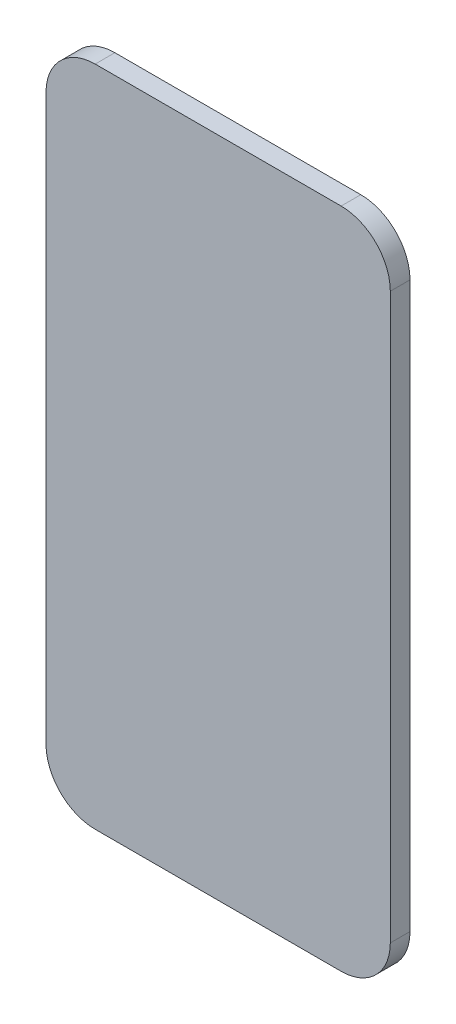
SolidWorks part; units mm, degrees
ref_plane "Front Plane" through (0, 0, 0) normal (0, 0, 1) x (1, 0, 0)
ref_plane "Top Plane" through (0, 0, 0) normal (0, 1, 0) x (1, 0, 0)
ref_plane "Right Plane" through (0, 0, 0) normal (1, 0, 0) x (0, 0, -1)
sketch "Sketch1" plane through (0, 0, 0) normal (0, 0, 1) x (1, 0, 0)
  line L1 (0, 0) -> (700, 0)
  line L2 (0, 0) -> (0, 1347.4093)
  line L3 (0, 1347.4093) -> (700, 1347.4093)
  line L4 (700, 0) -> (700, 1347.4093)
  dimension "D1" = 700
extrude "Boss-Extrude1" add sketch "Sketch1" along normal blind 40
fillet "Fillet1" radius 100 4 edges at (700, 0, 20) (0, 0, 20) (0, 1347.4093, 20) (700, 1347.4093, 20)
